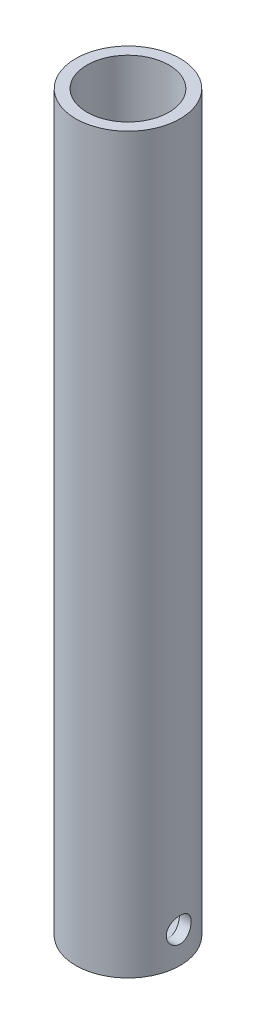
SolidWorks part; units mm, degrees
material "6063-T5"
ref_plane "Front Plane" through (0, 0, 0) normal (0, 0, 1) x (1, 0, 0)
ref_plane "Top Plane" through (0, 0, 0) normal (0, 1, 0) x (1, 0, 0)
ref_plane "Right Plane" through (0, 0, 0) normal (1, 0, 0) x (0, 0, -1)
sketch "Sketch1" plane through (0, 0, 0) normal (0, 1, 0) x (1, 0, 0)
  circle A0 centre (0, 0) radius 10.4648
  circle A1 centre (0, 0) radius 13.335
  dimension "D1" = 20.9296
  dimension "D2" = 26.67
extrude "Boss-Extrude1" add sketch "Sketch1" along normal blind 187.325
extrude "Boss-Extrude2" add sketch "Sketch1<2>" along normal blind 4.7625 contours A0
sketch "Sketch1<2>" plane through (0, 0, 0) normal (0, 1, 0) x (1, 0, 0) same geometry as "Sketch1"
ref_plane "Plane1" through (13.335, 0, 0) normal (1, 0, 0) x (0, 0, -1)
sketch "Sketch3" plane through (13.335, 0, 0) normal (1, 0, 0) x (0, 0, -1)
  line L0 (0, -187.325) -> (0, 187.325) construction
  line L1 (13.335, 187.325) -> (-13.335, 187.325) construction
  line L2 (-13.335, 0) -> (13.335, 0) construction
  circle A0 centre (0, 7.9375) radius 3.175
  point P0 (0, 7.9375)
  point P6 (0, 0)
  dimension "D2" = 6.35
  dimension "D1" = 7.9375
extrude "Cut-Extrude1" cut sketch "Sketch3" against normal blind 14.351
